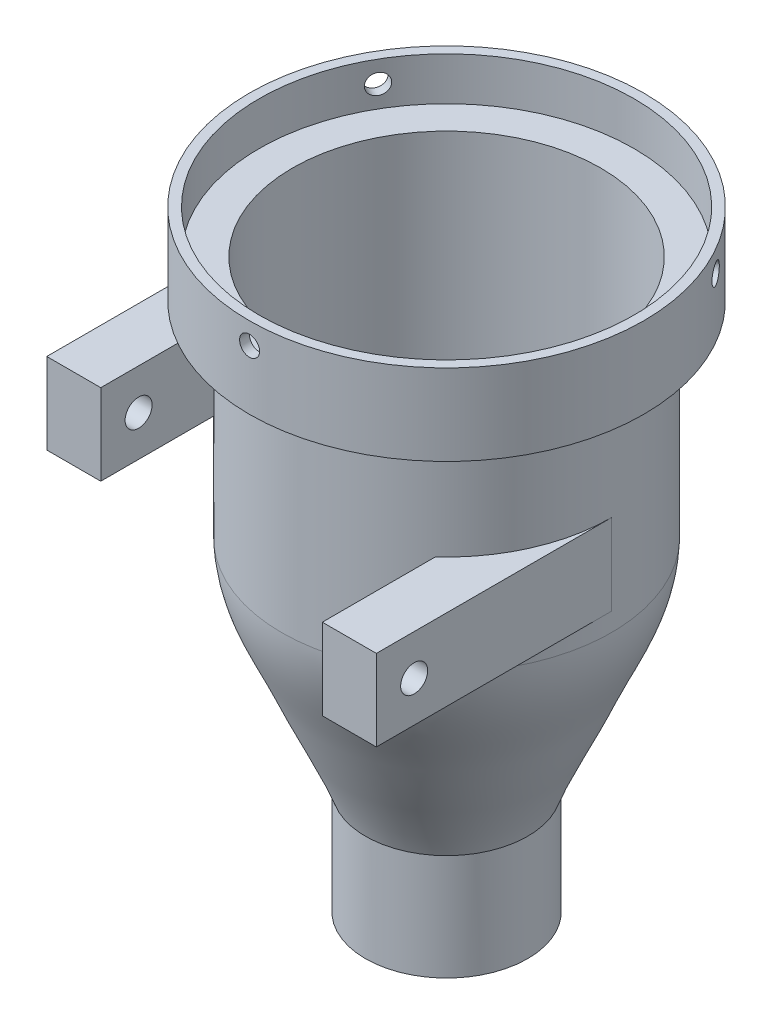
SolidWorks part; units mm, degrees
ref_plane "Płaszczyzna przednia" through (0, 0, 0) normal (0, 0, 1) x (1, 0, 0)
ref_plane "Płaszczyzna górna" through (0, 0, 0) normal (0, 1, 0) x (1, 0, 0)
ref_plane "Płaszczyzna prawa" through (0, 0, 0) normal (1, 0, 0) x (0, 0, -1)
sketch "Sketch1" plane through (0, 0, 0) normal (0, 1, 0) x (1, 0, 0)
  circle A0 centre (0, 0) radius 12.6
  circle A1 centre (0, 0) radius 11.1
  dimension "D1" = 25.2
  dimension "D2" = 1.5
extrude "Boss-Extrude1" add sketch "Sketch1" against normal blind 0.001
ref_plane "Plane1" through (0, 50, 0) normal (0, 1, 0) x (1, 0, 0)
sketch "Sketch2" plane through (0, 50, 0) normal (0, 1, 0) x (1, 0, 0)
  circle A0 centre (0, 0) radius 28.5
  circle A1 centre (0, 0) radius 30.5
  dimension "D1" = 57
  dimension "D2" = 2
extrude "Boss-Extrude2" add sketch "Sketch2" along normal blind 45 separate body contours A1 | A0
sketch "Sketch6" plane through (0, 0, 0) normal (1, 0, 0) x (0, 0, -1)
  line L1 (-52.0025, 57.5992) -> (47.7591, 57.5992)
  line L2 (-52.0025, 57.5992) -> (-52.0025, -12.321)
  line L3 (-52.0025, -12.321) -> (47.7591, -12.321)
  line L4 (47.7591, 57.5992) -> (47.7591, -12.321)
  line L7 (12.6, 0) -> (11.1, 0)
  line L8 (30.5, 50) -> (28.5, 50)
  line L9 (-28.5, 50) -> (-30.5, 50)
  line L10 (-28.5, 50) -> (-30.5, 50)
  line L11 (30.5, 50) -> (28.5, 50)
  line L12 (0, 0) -> (0, 60.1889) construction
  spline S0 degree 3 poles (12.6, 0) (14.219, 10.4067) (19.2483, 18.8627) (26.0867, 35.4758) (30.1864, 42.333) (30.5, 50) knots 0 0 0 0 0.476692 0.576692 1 1 1 1
  spline S1 degree 3 poles (11.1, 0) (11.5156, 8.4627) (16.3414, 17.4201) (23.8596, 35.0286) (27.0601, 41.7039) (28.5, 50) knots 0 0 0 0 0.530324 0.630324 1 1 1 1
revolve "Revolve2" add sketch "Sketch6" angle 360 about L12 region at (0, 26.2521, -21.1238)
sketch "Sketch7" plane through (0, 95, 0) normal (0, 1, 0) x (1, 0, 0)
  circle A0 centre (0, 0) radius 34.7
  circle A1 centre (0, 0) radius 30.5 construction
  circle A2 centre (0, 0) radius 36.5
  circle A3 centre (0, 0) radius 36.5
  circle M2 centre (0, 0) radius 30.5
  dimension "D2" = 4.2
  dimension "D1" = 6
extrude "Boss-Extrude3" add sketch "Sketch7" against normal blind 7 separate body contours A3 M2 | A3 A0 region at (-33.7185, 95, 0) region at (-35.4676, 95, 0)
sketch "Sketch8" plane through (0, 0, 0) normal (0, 1, 0) x (1, 0, 0)
  circle A0 centre (0, 0) radius 15.0116
  circle A1 centre (0, 0) radius 12.6
extrude "Boss-Extrude4" add sketch "Sketch8" along normal up to surface (9.6199 mm away) contours A0 | A1 up to face at (0, 50, 30.5)
ref_axis "Axis1" through (0, 95, 0) along (0, -1, 0)
extrude "Boss-Extrude5" add sketch "Sketch7<3>" along normal blind 8 contours A0 | A3
sketch "Sketch7<3>" plane through (0, 95, 0) normal (0, 1, 0) x (1, 0, 0) same geometry as "Sketch7"
ref_plane "Plane2" through (0, 0, 36.5) normal (0, 0, 1) x (1, 0, 0)
sketch "Sketch14" plane through (0, 0, 36.5) normal (0, 0, 1) x (1, 0, 0)
  line L0 (0, 103) -> (0, 95) construction
  line L1 (34.7, 103) -> (-34.7, 103) construction
  line L2 (34.7, 95) -> (-34.7, 95) construction
  circle A0 centre (0, 99) radius 1.85
  point P0 (0, 99)
  dimension "D1" = 3.7
extrude "Cut-Extrude1" cut sketch "Sketch14" against normal blind 8 contours A0
pattern_circular "CirPattern1" count 3 over 360 about axis through (0, 103, 0) along (0, 1, 0) of "Cut-Extrude1"
sketch "Sketch16" plane through (0, 0, 36.5) normal (0, 0, 1) x (1, 0, 0)
  line L0 (-30.5, 88) -> (-30.5, 50) construction
  line L1 (-30.5, 85.526) -> (-20.5, 85.526)
  line L2 (-30.5, 85.526) -> (-30.5, 70.526)
  line L3 (-30.5, 70.526) -> (-20.5, 70.526)
  line L4 (-20.5, 85.526) -> (-20.5, 70.526)
  line L5 (30.5, 50) -> (30.5, 88) construction
  line L6 (20.5, 68.4363) -> (30.5, 68.4363)
  line L7 (20.5, 68.4363) -> (20.5, 53.4363)
  line L8 (20.5, 53.4363) -> (30.5, 53.4363)
  line L9 (30.5, 68.4363) -> (30.5, 53.4363)
  dimension "D1" = 15
  dimension "D2" = 15
  dimension "D3" = 10
extrude "Boss-Extrude6" add sketch "Sketch16" against normal up to next and the other way blind 7
sketch "Sketch17" plane through (-30.5, 0, 0) normal (-1, 0, 0) x (0, 0, 1)
  line L0 (43.5, 85.526) -> (43.5, 70.526) construction
  line L1 (36.5, 85.526) -> (36.5, 70.526) construction
  line L2 (43.5, 85.526) -> (0, 85.526) construction
  line L3 (43.5, 70.526) -> (0, 70.526) construction
  line L4 (36.5, 53.4363) -> (36.5, 68.4363) construction
  line L5 (43.5, 68.4363) -> (22.5832, 68.4363) construction
  line L6 (43.5, 53.4363) -> (22.5832, 53.4363) construction
  line L7 (43.5, 68.4363) -> (43.5, 53.4363) construction
  circle A0 centre (36.5, 78.026) radius 2.5
  circle A1 centre (36.5, 60.9363) radius 2.5
  point P10 (0, 0)
  point P15 (41.7332, 62.1671)
  point P16 (41.763, 68.4363)
  point P19 (41.3037, 53.4363)
  dimension "D1" = 5
  dimension "D3" = 5
  dimension "D2" = 7
  dimension "D4" = 7
extrude "Cut-Extrude2" cut sketch "Sketch17" against normal through all
extrude "Boss-Extrude7" add sketch "Sketch8<5>" against normal blind 10
sketch "Sketch8<5>" plane through (0, 0, 0) normal (0, 1, 0) x (1, 0, 0) same geometry as "Sketch8"
